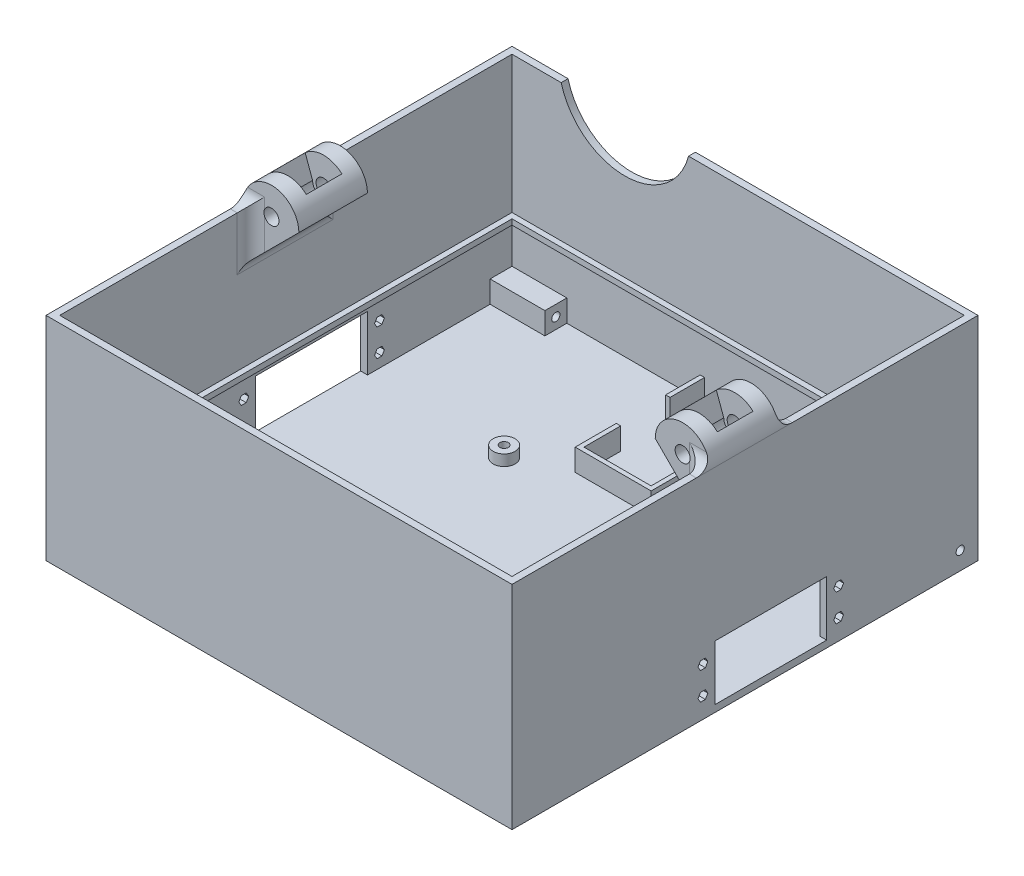
SolidWorks part; units mm, degrees
material "ABS"
ref_plane "Front Plane" through (0, 0, 0) normal (0, 0, 1) x (1, 0, 0)
ref_plane "Top Plane" through (0, 0, 0) normal (0, 1, 0) x (1, 0, 0)
ref_plane "Right Plane" through (0, 0, 0) normal (1, 0, 0) x (0, 0, -1)
sketch "Sketch1" plane through (0, 0, 0) normal (0, 1, 0) x (1, 0, 0)
  line L0 (85, 117.5) -> (85, 0) construction
  line L1 (0, 0) -> (170, 0)
  line L2 (0, 0) -> (0, 170)
  line L4 (170, 0) -> (170, 170)
  line L5 (0, 85) -> (170, 85) construction
  line L6 (170, 105.4) -> (170, 64.6) construction
  line L7 (50, 117.5) -> (120, 117.5) construction
  line L8 (50, 117.5) -> (50, 52.5) construction
  line L9 (50, 52.5) -> (120, 52.5) construction
  line L10 (120, 117.5) -> (120, 52.5) construction
  line L15 (73, 167.25) -> (97, 167.25) construction
  line L16 (73, 167.25) -> (73, 123.75) construction
  line L17 (73, 123.75) -> (97, 123.75) construction
  line L18 (97, 167.25) -> (97, 123.75) construction
  line L19 (0, 105.4) -> (26.8, 105.4) construction
  line L20 (0, 105.4) -> (0, 64.6) construction
  line L21 (0, 64.6) -> (26.8, 64.6) construction
  line L22 (26.8, 105.4) -> (26.8, 64.6) construction
  line L23 (170, 64.6) -> (143.2, 64.6) construction
  line L24 (170, 105.4) -> (143.2, 105.4) construction
  line L25 (143.2, 105.4) -> (143.2, 64.6) construction
  line L30 (56, 46.25) -> (80, 46.25) construction
  line L31 (56, 46.25) -> (56, 2.75) construction
  line L32 (56, 2.75) -> (80, 2.75) construction
  line L33 (80, 46.25) -> (80, 2.75) construction
  line L36 (0, 170) -> (170, 170)
  line L37 (85, 117.5) -> (85, 170) construction
  line L38 (55, 165) -> (60, 165) construction
  line L39 (55, 165) -> (55, 60) construction
  line L40 (55, 60) -> (60, 60) construction
  line L41 (60, 165) -> (60, 60) construction
  circle A0 centre (105, 27.5) radius 8.25 construction
  dimension "D7" = 16.5
  dimension "D1" = 170
  dimension "D2" = 170
  dimension "D3" = 70
  dimension "D4" = 65
  dimension "D5" = 35
  dimension "D6" = 32.5
  dimension "D8" = 25
  dimension "D9" = 26.8
  dimension "D10" = 40.8
  dimension "D11" = 20.4
  dimension "D12" = 24
  dimension "D13" = 43.5
  dimension "D14" = 2.75
  dimension "D15" = 12
  dimension "D16" = 24
  dimension "D17" = 43.5
  dimension "D18" = 2.75
  dimension "D19" = 5
  dimension "D20" = 20
  dimension "D21" = 5
  dimension "D22" = 105
  dimension "D23" = 5
  dimension "D24" = 25
extrude "Boss-Extrude1" add sketch "Sketch1" along normal blind 2.5
sketch "Sketch2" plane through (0, 2.5, 0) normal (0, 1, 0) x (1, 0, 0)
  line L0 (120, 117.5) -> (120, 52.5) construction
  line L1 (50, 52.5) -> (120, 52.5) construction
  line L2 (50, 117.5) -> (50, 52.5) construction
  line L3 (50, 117.5) -> (120, 117.5) construction
  line L4 (0, 0) -> (170, 0)
  line L5 (170, 0) -> (170, 170)
  line L6 (170, 170) -> (0, 170)
  line L7 (0, 170) -> (0, 0)
  line L8 (0, 0) -> (170, 0)
  line L9 (170, 0) -> (170, 170)
  line L10 (170, 170) -> (0, 170)
  line L11 (0, 170) -> (0, 0)
  line L12 (120, 117.5) -> (120, 52.5) construction
  line L13 (50, 52.5) -> (120, 52.5) construction
  line L14 (50, 117.5) -> (50, 52.5) construction
  line L15 (50, 117.5) -> (120, 117.5) construction
  circle A0 centre (105, 27.5) radius 8.25 construction
  circle A1 centre (105, 27.5) radius 8.25 construction
  circle A2 centre (53.523, 113.6) radius 1.55
  circle A3 centre (53.5, 56) radius 1.55
  circle A4 centre (116.5, 56) radius 1.55
  circle A5 centre (105, 27.5) radius 8.25
  dimension "D2" = 3.1
  dimension "D3" = 3.1
  dimension "D4" = 3.1
  dimension "D5" = 3.5
  dimension "D6" = 3.5
  dimension "D7" = 3.5
  dimension "D8" = 3.5
  dimension "D9" = 3.523
  dimension "D10" = 3.9
  dimension "D1" = 0
extrude "Cut-Extrude2" cut sketch "Sketch2" against normal blind 2.5 contours A5 | A2 | A3 | A4 region at (105, 2.5, -27.5)
sketch "Sketch3" plane through (0, 2.5, 0) normal (0, 1, 0) x (1, 0, 0)
  line L0 (50, 52.5) -> (120, 52.5) construction
  line L1 (50, 117.5) -> (50, 52.5) construction
  line L2 (120, 117.5) -> (120, 52.5) construction
  line L3 (50, 117.5) -> (120, 117.5) construction
  line L4 (73, 167.25) -> (97, 167.25) construction
  line L6 (73, 123.75) -> (97, 123.75) construction
  line L7 (73, 167.25) -> (73, 123.75) construction
  line L8 (56, 2.75) -> (80, 2.75) construction
  line L9 (80, 46.25) -> (80, 2.75) construction
  line L10 (56, 46.25) -> (80, 46.25) construction
  line L11 (56, 46.25) -> (56, 2.75) construction
  line L12 (50, 52.5) -> (120, 52.5) construction
  line L13 (50, 117.5) -> (50, 52.5) construction
  line L14 (120, 117.5) -> (120, 52.5) construction
  line L15 (50, 117.5) -> (120, 117.5) construction
  line L16 (73, 167.25) -> (97, 167.25) construction
  line L18 (73, 123.75) -> (97, 123.75) construction
  line L19 (73, 167.25) -> (73, 123.75) construction
  line L20 (56, 2.75) -> (80, 2.75) construction
  line L21 (80, 46.25) -> (80, 2.75) construction
  line L22 (56, 46.25) -> (80, 46.25) construction
  line L23 (56, 46.25) -> (56, 2.75) construction
  line L24 (71.15, 167.5) -> (72.75, 167.5)
  line L26 (72.75, 167.5) -> (72.75, 154.9)
  line L27 (72.75, 123.5) -> (97.25, 123.5)
  line L28 (97.25, 167.5) -> (97.25, 154.9)
  line L30 (71.15, 167.5) -> (71.15, 154.9)
  line L31 (71.15, 121.9) -> (98.85, 121.9)
  line L32 (98.85, 167.5) -> (98.85, 154.9)
  line L33 (55.75, 46.5) -> (80.25, 46.5)
  line L34 (55.75, 46.5) -> (55.75, 33.1)
  line L36 (80.25, 46.5) -> (80.25, 33.1)
  line L38 (81.85, 2.5) -> (81.85, 15.1)
  line L39 (81.85, 48.1) -> (54.15, 48.1)
  line L40 (54.15, 2.5) -> (54.15, 15.1)
  line L41 (0, 170) -> (170, 170)
  line L42 (0, 170) -> (0, 0)
  line L43 (0, 0) -> (170, 0)
  line L44 (170, 170) -> (170, 0)
  line L45 (2.5, 167.5) -> (167.5, 167.5)
  line L46 (2.5, 167.5) -> (2.5, 2.5)
  line L47 (2.5, 2.5) -> (167.5, 2.5)
  line L48 (167.5, 167.5) -> (167.5, 2.5)
  line L49 (97.25, 167.5) -> (98.85, 167.5)
  line L50 (72.75, 136.9) -> (72.75, 123.5)
  line L51 (71.15, 154.9) -> (72.75, 154.9)
  line L53 (71.15, 136.9) -> (72.75, 136.9)
  line L55 (97.25, 154.9) -> (98.85, 154.9)
  line L57 (97.25, 136.9) -> (98.85, 136.9)
  line L59 (71.15, 136.9) -> (71.15, 121.9)
  line L60 (97.25, 136.9) -> (97.25, 123.5)
  line L61 (98.85, 136.9) -> (98.85, 121.9)
  line L62 (55.75, 2.5) -> (54.15, 2.5)
  line L63 (80.25, 2.5) -> (81.85, 2.5)
  line L64 (55.75, 15.1) -> (55.75, 2.5)
  line L65 (54.15, 33.1) -> (55.75, 33.1)
  line L67 (54.15, 15.1) -> (55.75, 15.1)
  line L69 (80.25, 33.1) -> (81.85, 33.1)
  line L71 (80.25, 15.1) -> (81.85, 15.1)
  line L73 (54.15, 33.1) -> (54.15, 48.1)
  line L74 (80.25, 15.1) -> (80.25, 2.5)
  line L75 (81.85, 33.1) -> (81.85, 48.1)
  line L76 (97, 167.25) -> (97, 123.75) construction
  line L78 (4.5, 165.5) -> (165.5, 165.5)
  line L79 (4.5, 165.5) -> (4.5, 4.5)
  line L80 (4.5, 4.5) -> (165.5, 4.5)
  line L81 (165.5, 165.5) -> (165.5, 4.5)
  circle A0 centre (108, 109.5) radius 3
  circle A1 centre (53.523, 113.6) radius 4
  circle A2 centre (53.5, 56) radius 4
  circle A3 centre (116.5, 56) radius 4
  point P10 (98.05, 167.5)
  point P58 (54.95, 33.1)
  point P71 (72.75, 130.2)
  circle M60 centre (53.523, 113.6) radius 1.55
  circle M61 centre (53.5, 56) radius 1.55
  circle M62 centre (116.5, 56) radius 1.55
  line M63 (0, 170) -> (0, 0)
  line M64 (0, 0) -> (170, 0)
  line M65 (170, 0) -> (170, 170)
  line M66 (170, 170) -> (0, 170)
  dimension "D17" = 6
  dimension "D28" = 8
  dimension "D29" = 8
  dimension "D30" = 8
  dimension "D1" = 24.5
  dimension "D3" = 44
  dimension "D4" = 1.6
  dimension "D5" = 18
  dimension "D6" = 1.6
  dimension "D7" = 27.7
  dimension "D8" = 18
  dimension "D9" = 1.6
  dimension "D10" = 44
  dimension "D11" = 24.5
  dimension "D12" = 0.25
  dimension "D13" = 27.7
  dimension "D14" = 15
  dimension "D15" = 15
  dimension "D16" = 1.6
  dimension "D18" = 8
  dimension "D19" = 12
  dimension "D20" = 2.5
  dimension "D21" = 2.5
  dimension "D22" = 2.5
  dimension "D23" = 2.5
  dimension "D24" = 15
  dimension "D25" = 15
  dimension "D26" = 18
  dimension "D27" = 18
  dimension "D31" = 2
  dimension "D32" = 2
  dimension "D33" = 2
  dimension "D34" = 2
  dimension "D35" = 0.25
extrude "Boss-Extrude2" add sketch "Sketch3" along normal blind 8 contours L26 L51 L30 L24 | L28 L55 L32 L49 | L31 L61 L57 L60 L27 L50 L53 L59 | L73 L39 L75 L69 L36 L33 L34 L65 | L40 L67 L64 L62 | L38 L71 L74 L63
extrude "Boss-Extrude3" add sketch "Sketch3<3>" along normal blind 4 contours A1 M60 | A2 M61 | A3 M62 | A0 region at (49.6361, 2.5, -113.6) region at (49.6131, 2.5, -56) region at (112.6131, 2.5, -56)
sketch "Sketch3<3>" plane through (0, 2.5, 0) normal (0, 1, 0) x (1, 0, 0) same geometry as "Sketch3"
extrude "Boss-Extrude4" add sketch "Sketch3<4>" along normal blind 75 contours L45 L48 L47 L46 L24 M66 M63 M64 M65 region at (85, 2.5, -167.5958)
sketch "Sketch3<4>" plane through (0, 2.5, 0) normal (0, 1, 0) x (1, 0, 0) same geometry as "Sketch3"
extrude "Boss-Extrude5" add sketch "Sketch3<5>" along normal blind 2 from offset 23 contours L80 L79 L78 L30 L45 L46 L47 L40 | L78 L81 L80 L38 L47 L48 L45 L32 | L26 L78 L28 L45 | L28 L78 L32 L45 | L30 L78 L26 L24 | L80 L64 L47 L74 | L80 L74 L47 L38 | L80 L40 L47 L64 region at (71.95, 2.5, -166.5) region at (69.3629, 2.5, -166.5) region at (85, 2.5, -166.5) region at (98.05, 2.5, -166.5) region at (133.175, 2.5, -165.6409) region at (54.95, 2.5, -3.5) region at (68, 2.5, -3.5) region at (81.05, 2.5, -3.5)
sketch "Sketch3<5>" plane through (0, 2.5, 0) normal (0, 1, 0) x (1, 0, 0) same geometry as "Sketch3"
sketch "Sketch4" plane through (0, 0, 0) normal (-1, 0, 0) x (0, 0, 1)
  line L0 (-85, 0) -> (-85, 77.5) construction
  line L1 (-170, 0) -> (0, 0) construction
  line L2 (-170, 77.5) -> (0, 77.5) construction
  line L3 (-119.15, 18.9879) -> (-119.15, 4.1731) construction
  line L4 (-114.8, 22.6) -> (-74, 22.6)
  line L5 (-114.8, 22.6) -> (-114.8, 2.5)
  line L6 (-114.8, 2.5) -> (-74, 2.5)
  line L7 (-74, 22.6) -> (-74, 2.5)
  line L8 (-117.3602, 17.4379) -> (-118.2551, 18.9879)
  line L9 (-118.2551, 18.9879) -> (-120.0449, 18.9879)
  line L10 (-120.0449, 18.9879) -> (-120.9398, 17.4379)
  line L11 (-120.9398, 17.4379) -> (-120.0449, 15.8879)
  line L12 (-120.0449, 15.8879) -> (-118.2551, 15.8879)
  line L13 (-118.2551, 15.8879) -> (-117.3602, 17.4379)
  line L14 (-117.3602, 7.4379) -> (-118.2551, 8.9879)
  line L15 (-118.2551, 8.9879) -> (-120.0449, 8.9879)
  line L16 (-120.0449, 8.9879) -> (-120.9398, 7.4379)
  line L17 (-120.9398, 7.4379) -> (-120.0449, 5.8879)
  line L18 (-120.0449, 5.8879) -> (-118.2551, 5.8879)
  line L19 (-118.2551, 5.8879) -> (-117.3602, 7.4379)
  line L44 (-94.4, 22.6) -> (-94.4, 2.5) construction
  line L45 (-70.5449, 5.8879) -> (-71.4398, 7.4379)
  line L46 (-68.7551, 5.8879) -> (-70.5449, 5.8879)
  line L47 (-67.8602, 7.4379) -> (-68.7551, 5.8879)
  line L48 (-68.7551, 8.9879) -> (-67.8602, 7.4379)
  line L49 (-70.5449, 8.9879) -> (-68.7551, 8.9879)
  line L50 (-71.4398, 7.4379) -> (-70.5449, 8.9879)
  line L51 (-70.5449, 15.8879) -> (-71.4398, 17.4379)
  line L52 (-68.7551, 15.8879) -> (-70.5449, 15.8879)
  line L53 (-67.8602, 17.4379) -> (-68.7551, 15.8879)
  line L54 (-68.7551, 18.9879) -> (-67.8602, 17.4379)
  line L55 (-70.5449, 18.9879) -> (-68.7551, 18.9879)
  line L56 (-71.4398, 17.4379) -> (-70.5449, 18.9879)
  circle A4 centre (-119.15, 17.4379) radius 1.55 construction
  circle A5 centre (-119.15, 7.4379) radius 1.55 construction
  dimension "D5" = 4.35
  dimension "D7" = 3.1
  dimension "D8" = 3.1
  dimension "D1" = 40.8
  dimension "D2" = 11
  dimension "D3" = 20.1
  dimension "D4" = 2.5
  dimension "D9" = 10
extrude "Cut-Extrude3" cut sketch "Sketch4" against normal blind 12
extrude "Cut-Extrude4" cut sketch "Sketch4<2>" against normal blind 12 from surface starting at face at (167.5, 14, -85)
sketch "Sketch4<2>" plane through (0, 0, 0) normal (-1, 0, 0) x (0, 0, 1) same geometry as "Sketch4"
sketch "Sketch5" plane through (0, 2.5, 0) normal (0, 1, 0) x (1, 0, 0)
  line L1 (87.5, 38.8) -> (90, 38.8)
  line L2 (87.5, 38.8) -> (87.5, 18.6)
  line L3 (87.5, 18.6) -> (90, 18.6)
  line L4 (90, 38.8) -> (90, 18.6)
  line L5 (120, 38.8) -> (122.5, 38.8)
  line L6 (120, 38.8) -> (120, 18.6)
  line L7 (120, 18.6) -> (122.5, 18.6)
  line L8 (122.5, 38.8) -> (122.5, 18.6)
  line L9 (87.5, 38.8) -> (122.5, 38.8)
  line L10 (87.5, 38.8) -> (87.5, 18.6)
  line L11 (87.5, 18.6) -> (122.5, 18.6)
  line L12 (122.5, 38.8) -> (122.5, 18.6)
  circle A0 centre (105, 27.5) radius 8.25 construction
  circle M43 centre (105, 27.5) radius 8.25
  dimension "D1" = 30
  dimension "D2" = 2.5
  dimension "D3" = 2.5
  dimension "D4" = 15
  dimension "D5" = 11.3
  dimension "D6" = 20.2
  dimension "D7" = 20.2
  dimension "D8" = 11.3
extrude "Boss-Extrude6" add sketch "Sketch5" along normal blind 15.3 contours L4 L1 L2 L3 | L8 L5 L6 L7 region at (88.75, 2.5, -28.7) region at (121.25, 2.5, -28.7)
extrude "Boss-Extrude7" add sketch "Sketch5<3>" along normal blind 2.5 from surface contours L4 L11 L6 L9 M43 | L4 L1 L2 L3 | L8 L5 L6 L7 | M43 region at (88.75, 2.5, -28.7) region at (105, 2.5, -38.4383) region at (121.25, 2.5, -28.7) region at (105, 2.5, -27.5) starting at face at (88.75, 17.8, -28.7)
sketch "Sketch5<3>" plane through (0, 2.5, 0) normal (0, 1, 0) x (1, 0, 0) same geometry as "Sketch5"
sketch "Sketch6" plane through (0, 20.3, 0) normal (0, 1, 0) x (1, 0, 0)
  line L0 (122.5, 18.6) -> (122.5, 38.8) construction
  line L1 (93.85, 38.8) -> (116.15, 38.8) construction
  line L2 (93.85, 38.8) -> (93.85, 18.6) construction
  line L3 (93.85, 18.6) -> (116.15, 18.6) construction
  line L4 (116.15, 38.8) -> (116.15, 18.6) construction
  line L7 (122.5, 38.8) -> (87.5, 38.8) construction
  line L8 (93.85, 34.1599) -> (110.2376, 34.1599)
  line L10 (93.85, 38.8) -> (116.15, 38.8)
  line L11 (89.84, 38.8) -> (93.85, 38.8)
  line L12 (87.5, 18.6) -> (87.5, 38.8) construction
  line L13 (87.5, 18.6) -> (90.001, 18.6)
  line L14 (87.5, 18.6) -> (87.5, 25.6)
  line L15 (87.5, 25.6) -> (90.001, 25.6)
  line L16 (90.001, 18.6) -> (90.001, 25.6)
  circle A0 centre (113.7, 34.2) radius 1.55
  circle A1 centre (96.3, 20.8) radius 1.55
  arc A2 (113.7, 37.2) -> (110.7024, 34.3208) centre (113.7, 34.2) ccw
  arc A3 (116.15, 38.8) -> (113.7, 37.2) centre (113.6167, 40.0033) cw
  arc A4 (110.7024, 34.3208) -> (110.2376, 34.1599) centre (110.1681, 35.1129) cw
  arc A5 (93.85, 34.1599) -> (91.8634, 35.8823) centre (93.681, 35.9718) cw
  arc A6 (91.8634, 35.8823) -> (89.84, 38.8) centre (89.2189, 36.2088) ccw
  line M5 (87.5, 18.6) -> (122.5, 18.6)
  line M7 (122.5, 38.8) -> (87.5, 38.8)
  line M8 (87.5, 38.8) -> (87.5, 18.6)
  dimension "D4" = 3.1
  dimension "D5" = 3.1
  dimension "D10" = 6
  dimension "D11" = 2.501
  dimension "D1" = 22.3
  dimension "D2" = 20.2
  dimension "D3" = 6.35
  dimension "D6" = 2.45
  dimension "D7" = 4.6
  dimension "D8" = 2.2
  dimension "D9" = 2.45
  dimension "D12" = 7
extrude "Cut-Extrude5" cut sketch "Sketch6" against normal blind 2.5 contours A6 A5 L8 A4 A2 A3 M7 | A0 | A1 region at (102.3287, 20.3, -36.641) region at (113.7, 20.3, -34.2) region at (96.3, 20.3, -20.8)
extrude "Cut-Extrude6" cut sketch "Sketch6<3>" against normal up to surface (17.8 mm away) contours L16 L15 M5 M8 region at (88.7505, 20.3, -22.1) up to face at (121.25, 2.5, -28.7)
sketch "Sketch6<3>" plane through (0, 20.3, 0) normal (0, 1, 0) x (1, 0, 0) same geometry as "Sketch6"
sketch "Sketch7" plane through (0, 2.5, 0) normal (0, 1, 0) x (1, 0, 0)
  line L11 (2.5, 167.5) -> (22.5, 167.5)
  line L12 (2.5, 167.5) -> (2.5, 159.5)
  line L13 (2.5, 159.5) -> (22.5, 159.5)
  line L14 (22.5, 167.5) -> (22.5, 159.5)
  line L15 (167.5, 167.5) -> (147.5, 167.5)
  line L16 (167.5, 167.5) -> (167.5, 159.5)
  line L17 (167.5, 159.5) -> (147.5, 159.5)
  line L18 (147.5, 167.5) -> (147.5, 159.5)
  dimension "D1" = 20
  dimension "D2" = 20
  dimension "D3" = 8
  dimension "D4" = 8
extrude "Boss-Extrude8" add sketch "Sketch7" along normal blind 8
sketch "Sketch8" plane through (0, 0, 0) normal (-1, 0, 0) x (0, 0, 1)
  line L0 (-170, 77.5) -> (-170, 0) construction
  line L1 (-170, 0) -> (0, 0) construction
  circle A0 centre (-163.5, 6.5) radius 1.5
  dimension "D1" = 3
  dimension "D2" = 6.5
  dimension "D3" = 6.5
extrude "Cut-Extrude7" cut sketch "Sketch8" against normal up to surface (22.5 mm away) up to face at (22.5, 6.5, -163.5)
extrude "Cut-Extrude8" cut sketch "Sketch8<2>" against normal through all from surface starting at face at (147.5, 6.5, -163.5)
sketch "Sketch8<2>" plane through (0, 0, 0) normal (-1, 0, 0) x (0, 0, 1) same geometry as "Sketch8"
sketch "Sketch9" plane through (0, 0, 0) normal (0, 0, 1) x (1, 0, 0)
  line L0 (0, 57.5) -> (20, 77.5)
  line L1 (0, 77.5) -> (0, 0) construction
  line L2 (0, 77.5) -> (170, 77.5) construction
  line L4 (0, 77.5) -> (0, 57.5)
  line L5 (85, 0) -> (85, 132.8456) construction
  line L6 (0, 0) -> (170, 0) construction
  line L7 (170, 57.5) -> (150, 77.5)
  line L8 (170, 77.5) -> (170, 57.5)
  arc A0 (20, 77.5) -> (0, 77.5) centre (10, 77.5) ccw
  circle A1 centre (10, 77.5) radius 2.75
  circle A2 centre (160, 77.5) radius 2.75
  arc A3 (150, 77.5) -> (170, 77.5) centre (160, 77.5) cw
  dimension "D3" = 5.5
  dimension "D1" = 20
  dimension "D2" = 20
extrude "Boss-Extrude9" add sketch "Sketch9" against normal blind 25 from offset 72.25 offset against normal yes
fillet "Fillet1" radius 5 5 edges at (1.25, 77.5, -97.25) (2.5, 68.75, -97.25) (2.5, 60, -84.75) (1.25, 77.5, -72.25) (2.5, 68.75, -72.25)
fillet "Fillet2" radius 5 5 edges at (168.75, 77.5, -97.25) (167.5, 68.75, -97.25) (167.5, 60, -84.75) (168.75, 77.5, -72.25) (167.5, 68.75, -72.25)
sketch "Sketch12" plane through (0, 0, -72.25) normal (0, 0, 1) x (1, 0, 0)
  line L3 (14, 77.5) -> (17.9048, 88.2284)
  line L4 (6, 77.5) -> (2.095, 88.229)
  line L5 (2.095, 88.229) -> (17.9048, 88.2284)
  line L6 (85, 0) -> (85, 101.5145) construction
  line L7 (0, 0) -> (170, 0) construction
  line L8 (164, 77.5) -> (167.905, 88.229)
  line L9 (167.905, 88.229) -> (152.0952, 88.2284)
  line L10 (156, 77.5) -> (152.0952, 88.2284)
  arc A0 (6, 77.5) -> (14, 77.5) centre (10, 77.5) ccw
  arc A3 (164, 77.5) -> (156, 77.5) centre (160, 77.5) cw
  dimension "D1" = 8
extrude "Cut-Extrude9" cut sketch "Sketch12" against normal blind 13 from offset 6 offset against normal yes
sketch "Sketch13" plane through (0, 0, -170) normal (0, 0, -1) x (-1, 0, 0)
  circle A0 centre (-43.6769, 83.6487) radius 24.0354
extrude "Cut-Extrude10" cut sketch "Sketch13" against normal blind 13
